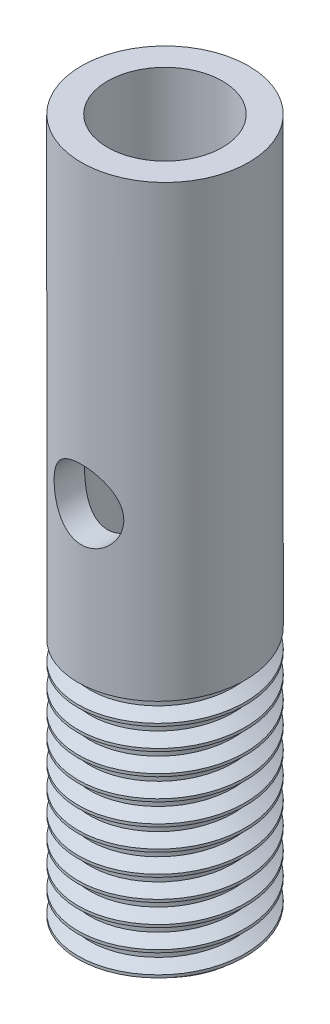
SolidWorks part; units mm, degrees
material "6061-O (SS)"
ref_plane "Plan de face" through (0, 0, 0) normal (0, 0, 1) x (1, 0, 0)
ref_plane "Plan de dessus" through (0, 0, 0) normal (0, 1, 0) x (1, 0, 0)
ref_plane "Plan de droite" through (0, 0, 0) normal (1, 0, 0) x (0, 0, -1)
sketch "Esquisse1" plane through (0, 0, 0) normal (0, 0, 1) x (1, 0, 0)
  line L0 (0, 0) -> (0, 40) construction
  line L1 (0, 0) -> (3.3, 0) construction
  line L2 (3.3, 0) -> (3.3, 40)
  line L3 (3.3, 40) -> (4.8, 40)
  line L4 (4.8, 40) -> (4.8, 0)
  line L5 (4.8, 0) -> (3.3, 0)
  line L6 (0, 40) -> (3.3, 40) construction
  dimension "D1" = 40
  dimension "D2" = 3.3
  dimension "D3" = 1.5
revolve "Révolution1" add sketch "Esquisse1" angle 360 about L0
thread "Filetage1" pitch 1.25 method cut profile "Profil de filetage1" start angle 0, offset 25, length 22, pitch 1.25, diameter 9.6
ref_plane "Plan1" through (-4.8, 15, 0) normal (0, 0, 1) x (-1, 0, 0)
sketch "Profil de filetage1" plane through (-4.8, 15, 0) normal (0, 0, 1) x (-1, 0, 0)
  line L0 (0, 0) -> (0, 1.25) construction
  line L11 (0, 0) -> (0, 1.0937)
  line L12 (0, 1.0937) -> (-0.6766, 0.7031)
  line L13 (-0.6766, 0.7031) -> (-0.6766, 0.3906)
  line L15 (-0.6766, 0.3906) -> (0, 0)
  line L17 (-0.6766, 0.5469) -> (0, 0.5469) construction
  point P2 (0, 0)
  dimension "Pitch" = 1.25
  dimension "Profile_Angle" = 60
  dimension "Profile_Land" = 0.3125
  dimension "Profile_Height" = 0.6766
sketch "Esquisse8" plane through (0, 0, 0) normal (0, 0, 1) x (1, 0, 0)
  line L0 (0, 0) -> (0, 23) construction
  circle A0 centre (0, 23) radius 2
  dimension "D2" = 4
  dimension "D1" = 23
extrude "Enlèv. mat.-Extru.1" cut sketch "Esquisse8" against normal through all and the other way through all
